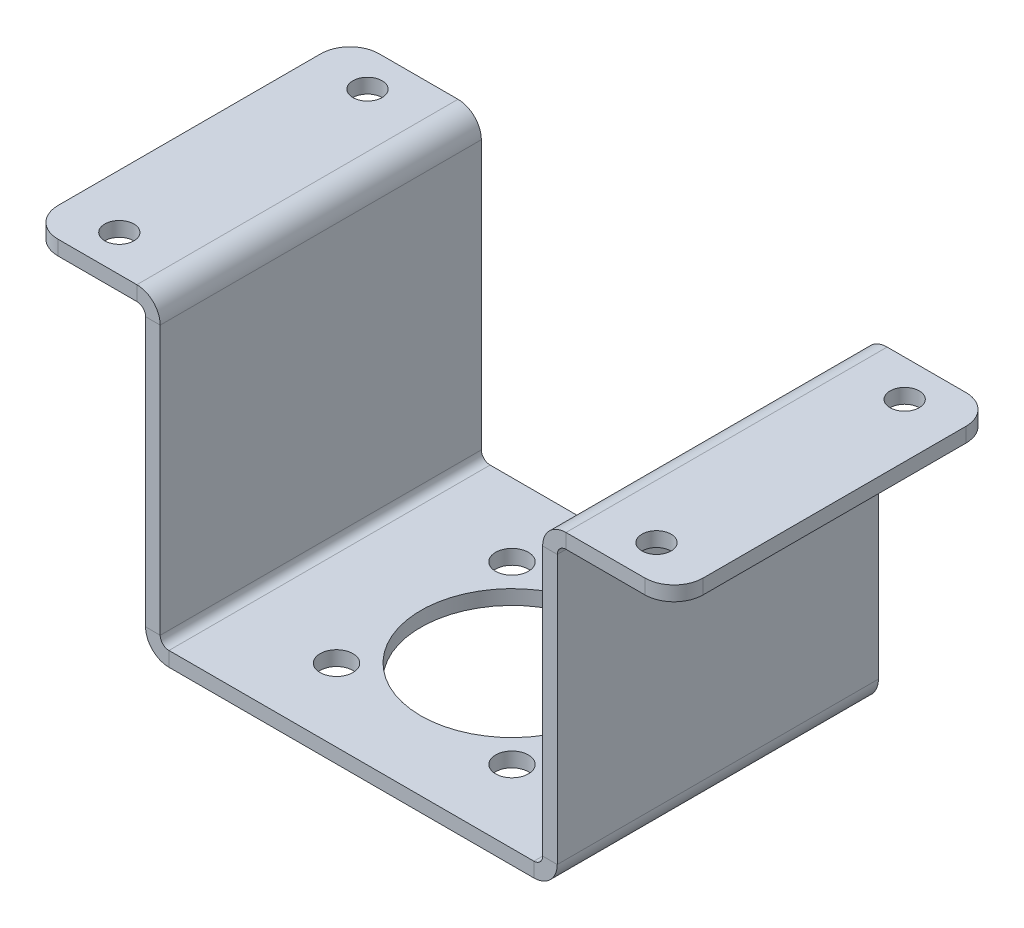
SolidWorks part; units mm, degrees
note: The reader was unsure of these and kept them because the rebuilt part matched: flange length of "Edge-Flange1", "Edge-Flange2".
material "Plain Carbon Steel"
ref_plane "Front Plane" through (0, 0, 0) normal (0, 0, 1) x (1, 0, 0)
ref_plane "Top Plane" through (0, 0, 0) normal (0, 1, 0) x (1, 0, 0)
ref_plane "Right Plane" through (0, 0, 0) normal (1, 0, 0) x (0, 0, -1)
sketch "Sketch1" plane through (0, 0, 0) normal (0, 1, 0) x (1, 0, 0)
  line L0 (20, 21) -> (20, -23)
  line L5 (45, -23) -> (45, 21) construction
  line L7 (20, 21) -> (70, 21)
  line L9 (20, -23) -> (70, -23)
  line L10 (70, 21) -> (70, -23)
  point P0 (0, 0)
  dimension "D2" = 44
  dimension "D3" = 50
base flange "Base-Flange1" sketch "Sketch1" thickness 2 reverse thickness direction no parameters "D1"=0.7366
edge flange "Edge-Flange1" sketch "Sketch13" flange profiles "Sketch13", "Sketch14" flange angle 90 flange length 40 flange position bend outside bend radius 1.2 thickness 2 relief rectangular parameters "D6"=10, "D8"=1
sketch "Sketch13" plane through (20, 0, 0) normal (-1, 0, 0) x (0, 0, 1)
  line L2 (-21, 0) -> (-21, 38)
  line L3 (-21, 38) -> (23, 38)
  line L4 (23, 38) -> (23, 0)
  line L7 (-21, 0) -> (23, 0) construction
  line L8 (-21, 0) -> (23, 0)
sketch "Sketch14" plane through (70, 0, 0) normal (1, 0, 0) x (0, 0, -1)
  line L2 (-23, 0) -> (-23, 38)
  line L3 (-23, 38) -> (21, 38)
  line L4 (21, 38) -> (21, 0)
  line L7 (-23, 0) -> (21, 0) construction
  line L8 (-23, 0) -> (21, 0)
bend "EdgeBend1" bend radius 1.2 bend angle 90 parameters "D5"=1
bend "EdgeBend2" bend radius 1.2 bend angle 90 parameters "D5"=2
edge flange "Edge-Flange2" sketch "Sketch19" flange profiles "Sketch19", "Sketch20" flange angle 90 flange length 18 flange position bend outside bend radius 1.2 thickness 2 relief rectangular parameters "D6"=10, "D8"=1
sketch "Sketch19" plane through (73.2, 38, 0) normal (0, 1, 0) x (0, 0, 1)
  line L2 (-21, 0) -> (-21, 16)
  line L3 (-21, 16) -> (23, 16)
  line L4 (23, 16) -> (23, 0)
  line L11 (-21, 0) -> (23, 0) construction
  line L12 (-21, 0) -> (23, 0)
sketch "Sketch20" plane through (16.8, 38, 0) normal (0, 1, 0) x (0, 0, -1)
  line L2 (-23, 0) -> (-23, 16)
  line L3 (-23, 16) -> (21, 16)
  line L4 (21, 16) -> (21, 0)
  line L7 (-23, 0) -> (21, 0) construction
  line L8 (-23, 0) -> (21, 0)
bend "EdgeBend3" bend radius 1.2 bend angle 90 parameters "D5"=3
bend "EdgeBend4" bend radius 1.2 bend angle 90 parameters "D5"=4
sketch "Sketch21" plane through (0, -2, 0) normal (0, -1, 0) x (1, 0, 0)
  line L0 (45, 23) -> (45, -21) construction
  line L1 (20, 23) -> (70, 23) construction
  line L2 (70, -21) -> (20, -21) construction
  line L3 (20, 1) -> (70, 1) construction
  line L4 (20, -21) -> (20, 23) construction
  line L5 (70, 23) -> (70, -21) construction
  circle A0 centre (45, 1) radius 12.5
  circle A1 centre (45, 1) radius 17 construction
  circle A3 centre (57.0208, 13.0208) radius 2.25
  circle A5 centre (57.0208, -11.0208) radius 2.25
  circle A7 centre (32.9792, -11.0208) radius 2.25
  circle A9 centre (32.9792, 13.0208) radius 2.25
  point P22 (42, 0)
extrude "Cut-Extrude1" cut sketch "Sketch21" against normal blind 2 normal cut yes
sketch "Sketch22" plane through (0, 39.2, 0) normal (0, -1, 0) x (1, 0, 0)
  line L0 (45, 23) -> (45, -21) construction
  line L1 (20, 23) -> (70, 23) construction
  line L2 (70, -21) -> (20, -21) construction
  line L3 (0.8, 23) -> (15.6, 23) construction
  line L4 (15.6, -21) -> (0.8, -21) construction
  line L5 (0.8, -21) -> (0.8, 23) construction
  circle A0 centre (8.2, 18) radius 2
  circle A1 centre (8.2, -16) radius 2
  circle A2 centre (81.8, -16) radius 2
  circle A3 centre (81.8, 18) radius 2
  dimension "D1" = 5
  dimension "D2" = 5
  dimension "D3" = 7.4
  dimension "D4" = 7.4
extrude "Cut-Extrude2" cut sketch "Sketch22" against normal blind 2 normal cut yes
fillet "Fillet1" radius 4 4 edges at (89.2, 40.2, 23) (89.2, 40.2, -21) (0.8, 40.2, -21) (0.8, 40.2, 23)
sketch "Bend-Lines1" [suppressed] plane through (0, 0, 0) normal (0, 1, 0) x (1, 0, 0)
sketch "Bounding-Box1" [suppressed] plane through (0, 0, 0) normal (0, 1, 0) x (1, 0, 0)
sheet metal parameters "Sheet-Metal1" thickness 2 parameters "D1"=0.7366
flat pattern "Flat-Pattern1" [suppressed]
sketch "Bend-Lines2" plane through (0, 0, 0) normal (0, 1, 0) x (1, 0, 0)
sketch3d "Bounding-Box2" [suppressed]
  line L0 (64, 21, 0) -> (20, 21, 0) construction
  line L1 (64, -23, 0) -> (20, -23, 0) construction
  line L2 (64, 21, 0) -> (64, -23, 0) construction
  line L3 (20, 21, 0) -> (20, -23, 0) construction
sheet metal parameters "Sheet-Metal4" thickness 2 parameters "D1"=0.7366
flat pattern "Flat-Pattern1"
sketch "Bend-Lines2" plane through (0, 0, 0) normal (0, 1, 0) x (1, 0, 0)
  line L0 (65.3639, -23) -> (65.3639, 21) construction
  line L1 (18.6361, 21) -> (18.6361, -23) construction
  line L2 (65.3639, -23) -> (65.3639, 21) construction
  line L3 (18.6361, 21) -> (18.6361, -23) construction
sketch3d "Bounding-Box2" [suppressed]
  line L0 (103.9912, 21, 0) -> (-19.9912, 21, 0) construction
  line L1 (103.9912, -23, 0) -> (-19.9912, -23, 0) construction
  line L2 (103.9912, 21, 0) -> (103.9912, -23, 0) construction
  line L3 (-19.9912, 21, 0) -> (-19.9912, -23, 0) construction
bend of the flat pattern "Flatten-<EdgeBend1>1"
bend of the flat pattern "Flatten-<EdgeBend2>1"
sheet metal parameters "Sheet-Metal5" thickness 2 parameters "D1"=0.7366
flat pattern "Flat-Pattern1"
sketch "Bend-Lines2" plane through (0, 0, 0) normal (0, 1, 0) x (1, 0, 0)
  line L0 (65.3639, -23) -> (65.3639, 21) construction
  line L1 (18.6361, 21) -> (18.6361, -23) construction
  line L2 (65.3639, -23) -> (65.3639, 21) construction
  line L3 (18.6361, 21) -> (18.6361, -23) construction
  line L4 (-21.3552, 21) -> (-21.3552, -23) construction
  line L5 (105.3552, -23) -> (105.3552, 21) construction
  line L6 (-21.3552, 21) -> (-21.3552, -23) construction
  line L7 (105.3552, -23) -> (105.3552, 21) construction
sketch3d "Bounding-Box2" [suppressed]
  line L0 (115.9825, 21, 0) -> (-31.9825, 21, 0) construction
  line L1 (115.9825, -23, 0) -> (-31.9825, -23, 0) construction
  line L2 (115.9825, 21, 0) -> (115.9825, -23, 0) construction
  line L3 (-31.9825, 21, 0) -> (-31.9825, -23, 0) construction
bend of the flat pattern "Flatten-<EdgeBend1>1"
bend of the flat pattern "Flatten-<EdgeBend2>1"
bend of the flat pattern "Flatten-<EdgeBend3>1"
bend of the flat pattern "Flatten-<EdgeBend4>1"
sheet metal parameters "Sheet-Metal6" thickness 2 parameters "D1"=0.7366
flat pattern "Flat-Pattern1"
sketch "Bend-Lines2" plane through (0, 0, 0) normal (0, 1, 0) x (1, 0, 0)
  line L0 (65.7279, -23) -> (65.7279, 21) construction
  line L1 (18.2721, 21) -> (18.2721, -23) construction
  line L2 (65.7279, -23) -> (65.7279, 21) construction
  line L3 (18.2721, 21) -> (18.2721, -23) construction
  line L4 (-21.9836, 21) -> (-21.9836, -23) construction
  line L5 (105.9836, -23) -> (105.9836, 21) construction
  line L6 (-21.9836, 21) -> (-21.9836, -23) construction
  line L7 (105.9836, -23) -> (105.9836, 21) construction
sketch3d "Bounding-Box2" [suppressed]
  line L0 (116.5115, 21, 0) -> (-32.5115, 21, 0) construction
  line L1 (116.5115, -23, 0) -> (-32.5115, -23, 0) construction
  line L2 (116.5115, 21, 0) -> (116.5115, -23, 0) construction
  line L3 (-32.5115, 21, 0) -> (-32.5115, -23, 0) construction
bend of the flat pattern "Flatten-<EdgeBend1>1"
bend of the flat pattern "Flatten-<EdgeBend2>1"
bend of the flat pattern "Flatten-<EdgeBend3>1"
bend of the flat pattern "Flatten-<EdgeBend4>1"
sheet metal parameters "Sheet-Metal7" thickness 2 parameters "D1"=0.7366
flat pattern "Flat-Pattern1"
sketch "Bend-Lines2" plane through (0, 0, 0) normal (0, 1, 0) x (1, 0, 0)
  line L0 (71.7279, -23) -> (71.7279, 21) construction
  line L1 (18.2721, 21) -> (18.2721, -23) construction
  line L2 (71.7279, -23) -> (71.7279, 21) construction
  line L3 (18.2721, 21) -> (18.2721, -23) construction
  line L4 (-21.9836, 21) -> (-21.9836, -23) construction
  line L5 (111.9836, -23) -> (111.9836, 21) construction
  line L6 (-21.9836, 21) -> (-21.9836, -23) construction
  line L7 (111.9836, -23) -> (111.9836, 21) construction
sketch3d "Bounding-Box2" [suppressed]
  line L0 (-38.5115, 20.9998, 0) -> (128.5115, 21, 0) construction
  line L1 (-38.5115, -23, 0) -> (128.5115, -22.9998, 0) construction
  line L2 (-38.5115, 20.9998, 0) -> (-38.5115, -23, 0) construction
  line L3 (128.5115, 21, 0) -> (128.5115, -22.9998, 0) construction
bend of the flat pattern "Flatten-<EdgeBend1>1"
bend of the flat pattern "Flatten-<EdgeBend2>1"
bend of the flat pattern "Flatten-<EdgeBend3>1"
bend of the flat pattern "Flatten-<EdgeBend4>1"
